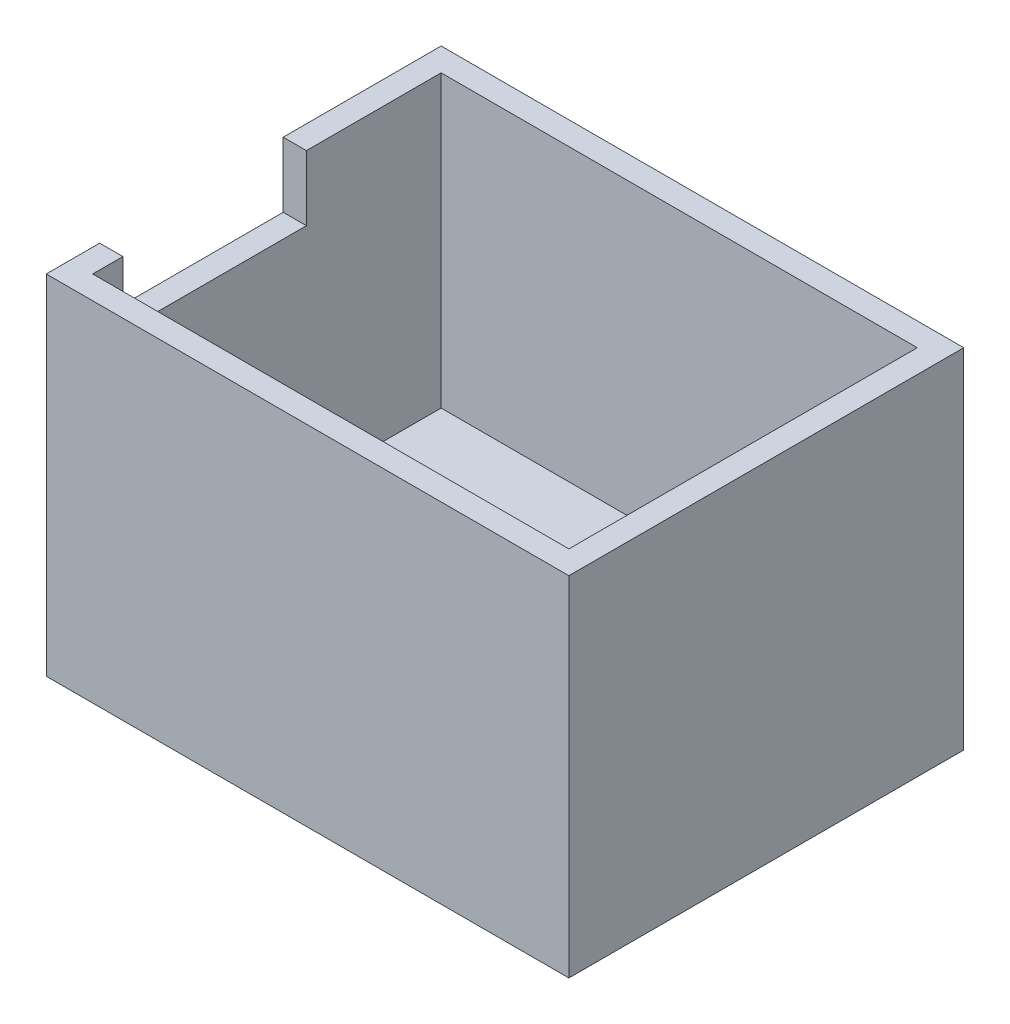
SolidWorks part; units mm, degrees
ref_plane "Front Plane" through (0, 0, 0) normal (0, 0, 1) x (1, 0, 0)
ref_plane "Top Plane" through (0, 0, 0) normal (0, 1, 0) x (1, 0, 0)
ref_plane "Right Plane" through (0, 0, 0) normal (1, 0, 0) x (0, 0, -1)
sketch "Sketch1" plane through (0, 0, 0) normal (0, 1, 0) x (1, 0, 0)
  line L1 (-28.575, -21.59) -> (28.575, -21.59)
  line L2 (-28.575, -21.59) -> (-28.575, 21.59)
  line L3 (-28.575, 21.59) -> (28.575, 21.59)
  line L4 (28.575, -21.59) -> (28.575, 21.59)
  line L5 (-28.575, -21.59) -> (28.575, 21.59) construction
  line L6 (-28.575, 21.59) -> (28.575, -21.59) construction
  point P0 (0, 0)
  dimension "D1" = 57.15
  dimension "D2" = 43.18
extrude "Boss-Extrude1" add sketch "Sketch1" along normal blind 38.1
sketch "Sketch2" plane through (0, 38.1, 0) normal (0, 1, 0) x (1, 0, 0)
  line L1 (26.035, -19.05) -> (-26.035, -19.05)
  line L2 (26.035, -19.05) -> (26.035, 19.05)
  line L3 (26.035, 19.05) -> (-26.035, 19.05)
  line L4 (-26.035, -19.05) -> (-26.035, 19.05)
  line L5 (26.035, -19.05) -> (-26.035, 19.05) construction
  line L6 (26.035, 19.05) -> (-26.035, -19.05) construction
  point P0 (0, 0)
  dimension "D1" = 38.1
  dimension "D2" = 52.07
extrude "Cut-Extrude1" cut sketch "Sketch2" against normal blind 31.75
sketch "Sketch3" plane through (0, 0, 0) normal (0, -1, 0) x (-1, 0, 0)
  line L0 (28.575, 0) -> (-28.575, 0) construction
  line L1 (7.493, -7.62) -> (-10.541, -7.62)
  line L2 (7.493, -7.62) -> (7.493, 7.62)
  line L3 (7.493, 7.62) -> (-10.541, 7.62)
  line L4 (-10.541, -7.62) -> (-10.541, 7.62)
  line L5 (7.493, -7.62) -> (-10.541, 7.62) construction
  line L6 (7.493, 7.62) -> (-10.541, -7.62) construction
  line L7 (28.575, 21.59) -> (28.575, -21.59) construction
  line L8 (-28.575, -21.59) -> (-28.575, 21.59) construction
  point P0 (-1.524, 0)
  dimension "D1" = 15.24
  dimension "D2" = 18.034
  dimension "D3" = 21.082
extrude "Cut-Extrude2" cut sketch "Sketch3" against normal through all
sketch "Sketch4" plane through (-28.575, 0, 0) normal (-1, 0, 0) x (0, 0, 1)
  line L0 (-21.59, 38.1) -> (21.59, 38.1) construction
  line L1 (15.748, 38.1) -> (-4.318, 38.1)
  line L2 (15.748, 38.1) -> (15.748, 30.988)
  line L3 (15.748, 30.988) -> (-4.318, 30.988)
  line L4 (-4.318, 38.1) -> (-4.318, 30.988)
  line L5 (21.59, 38.1) -> (21.59, 0) construction
  line L6 (-21.59, 38.1) -> (-21.59, 0) construction
  dimension "D1" = 5.842
  dimension "D2" = 17.272
  dimension "D3" = 7.112
extrude "Cut-Extrude3" cut sketch "Sketch4" against normal up to next
sketch "Sketch5" plane through (0, 0, 0) normal (0, -1, 0) x (1, 0, 0)
  line L1 (17.6249, -13.716) -> (24.2289, -13.716)
  line L2 (15.0849, -11.176) -> (15.0849, 11.176)
  line L3 (17.6249, 13.716) -> (24.2289, 13.716)
  line L4 (24.2289, -13.716) -> (24.2289, 13.716)
  line L5 (15.0849, -13.716) -> (24.2289, 13.716) construction
  line L6 (15.0849, 13.716) -> (24.2289, -13.716) construction
  arc A0 (15.0849, -11.176) -> (17.6249, -13.716) centre (17.6249, -11.176) ccw
  arc A1 (15.0849, 11.176) -> (17.6249, 13.716) centre (17.6249, 11.176) cw
  point P0 (19.6569, 0)
  dimension "D3" = 2.54
  dimension "D1" = 27.432
  dimension "D2" = 9.144
extrude "Cut-Extrude4" cut sketch "Sketch5" against normal up to next
hole_wizard "#4 Clearance Hole1" positions "Sketch7" profile "Sketch6" hole size "#4" standard "ANSI Inch" end condition through all
sketch "Sketch7" plane through (0, 0, 0) normal (0, -1, 0) x (-1, 0, 0)
  line L0 (-19.6569, 21.59) -> (-19.6569, -21.59) construction
  line L1 (-28.575, 21.59) -> (28.575, 21.59) construction
  line L2 (28.575, -21.59) -> (-28.575, -21.59) construction
  line L3 (-24.2289, 13.716) -> (-24.2289, -13.716) construction
  line L4 (-24.2289, 0) -> (-15.0849, 0) construction
  line L5 (-15.0849, -11.176) -> (-15.0849, 11.176) construction
  point P0 (-19.6569, 16.256)
  point P2 (-19.6569, -16.256)
  dimension "D1" = 4.572
  dimension "D2" = 32.512
sketch "Sketch6" plane through (19.6569, 0, -16.256) normal (1, 0, 0) x (0, 0, -1)
  line L0 (0, 0) -> (0, 38.1)
  line L1 (0, 38.1) -> (1.4732, 38.1)
  line L2 (1.4732, 38.1) -> (1.4732, 0)
  line L5 (1.4732, 0) -> (0, 0)
  line L11 (0, -6.35) -> (0, 107.95) construction
  dimension "Thru Hole Dia." = 2.9464
  dimension "Thru Hole Depth" = 38.1
hole_wizard "#6 Clearance Hole1" positions "Sketch9" profile "Sketch8" hole size "#6" standard "ANSI Inch" end condition through all
sketch "Sketch9" plane through (0, 0, 0) normal (0, -1, 0) x (-1, 0, 0)
  line L0 (3.175, -21.59) -> (3.175, 21.59) construction
  line L1 (28.575, -21.59) -> (-28.575, -21.59) construction
  line L2 (-28.575, 21.59) -> (28.575, 21.59) construction
  line L3 (28.575, 0) -> (-28.575, 0) construction
  line L4 (28.575, 21.59) -> (28.575, -21.59) construction
  line L5 (-28.575, -21.59) -> (-28.575, 21.59) construction
  point P0 (3.175, 14.605)
  point P2 (3.175, -14.605)
  dimension "D1" = 31.75
  dimension "D2" = 29.21
sketch "Sketch8" plane through (-3.175, 0, -14.605) normal (1, 0, 0) x (0, 0, -1)
  line L0 (0, 0) -> (0, 38.1)
  line L1 (0, 38.1) -> (1.8288, 38.1)
  line L2 (1.8288, 38.1) -> (1.8288, 0)
  line L5 (1.8288, 0) -> (0, 0)
  line L11 (0, -6.35) -> (0, 107.95) construction
  dimension "Thru Hole Dia." = 3.6576
  dimension "Thru Hole Depth" = 38.1
